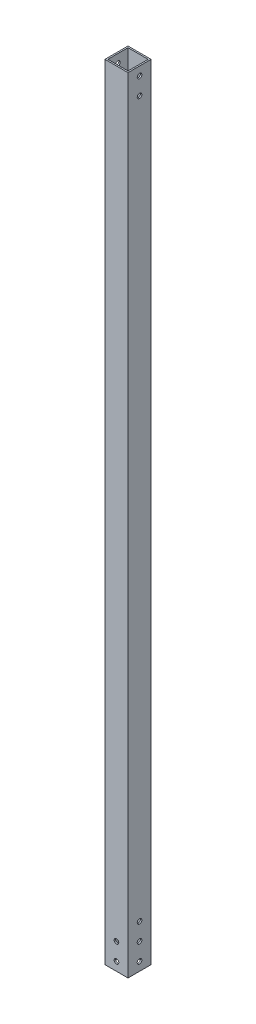
SolidWorks part; units mm, degrees
ref_plane "Front Plane" through (0, 0, 0) normal (0, 0, 1) x (1, 0, 0)
ref_plane "Top Plane" through (0, 0, 0) normal (0, 1, 0) x (1, 0, 0)
ref_plane "Right Plane" through (0, 0, 0) normal (1, 0, 0) x (0, 0, -1)
sketch "Sketch1" plane through (0, 0, 0) normal (0, 1, 0) x (1, 0, 0)
  line L0 (11.1125, 11.1125) -> (-11.1125, 11.1125)
  line L1 (12.7, -12.7) -> (-12.7, -12.7)
  line L2 (12.7, -12.7) -> (12.7, 12.7)
  line L3 (12.7, 12.7) -> (-12.7, 12.7)
  line L4 (-12.7, -12.7) -> (-12.7, 12.7)
  line L5 (12.7, -12.7) -> (-12.7, 12.7) construction
  line L6 (12.7, 12.7) -> (-12.7, -12.7) construction
  line L7 (-11.1125, -11.1125) -> (-11.1125, 11.1125)
  line L8 (11.1125, -11.1125) -> (-11.1125, -11.1125)
  line L9 (11.1125, -11.1125) -> (11.1125, 11.1125)
  point P0 (0, 0)
  dimension "D1" = 25.4
  dimension "D2" = 1.5875
extrude "Boss-Extrude1" add sketch "Sketch1" along normal blind 863.6
sketch "Sketch2" plane through (0, 0, 12.7) normal (0, 0, 1) x (1, 0, 0)
  line L0 (-12.7, 0) -> (12.7, 0) construction
  circle A0 centre (0, 9.525) radius 2.5527
  circle A1 centre (0, 28.575) radius 2.5527
  point P7 (0, 0)
  point P11 (0, 0)
  point P12 (0, 0)
  dimension "D1" = 9.525
  dimension "D2" = 19.05
  dimension "D3" = 5.1054
extrude "Cut-Extrude1" cut sketch "Sketch2" against normal through all
sketch "Sketch3" plane through (12.7, 0, 0) normal (1, 0, 0) x (0, 0, -1)
  line L0 (-12.7, 0) -> (12.7, 0) construction
  line L1 (-12.7, 863.6) -> (12.7, 863.6) construction
  circle A0 centre (0, 9.525) radius 2.5527
  circle A1 centre (0, 28.575) radius 2.5527
  circle A2 centre (0, 47.625) radius 2.5527
  circle A3 centre (0, 854.075) radius 2.5527
  circle A4 centre (0, 835.025) radius 2.5527
  point P9 (0, 0)
  point P13 (0, 0)
  dimension "D1" = 9.525
  dimension "D2" = 19.05
  dimension "D3" = 19.05
  dimension "D4" = 5.1054
  dimension "D5" = 9.525
  dimension "D6" = 19.05
extrude "Cut-Extrude2" cut sketch "Sketch3" against normal through all
